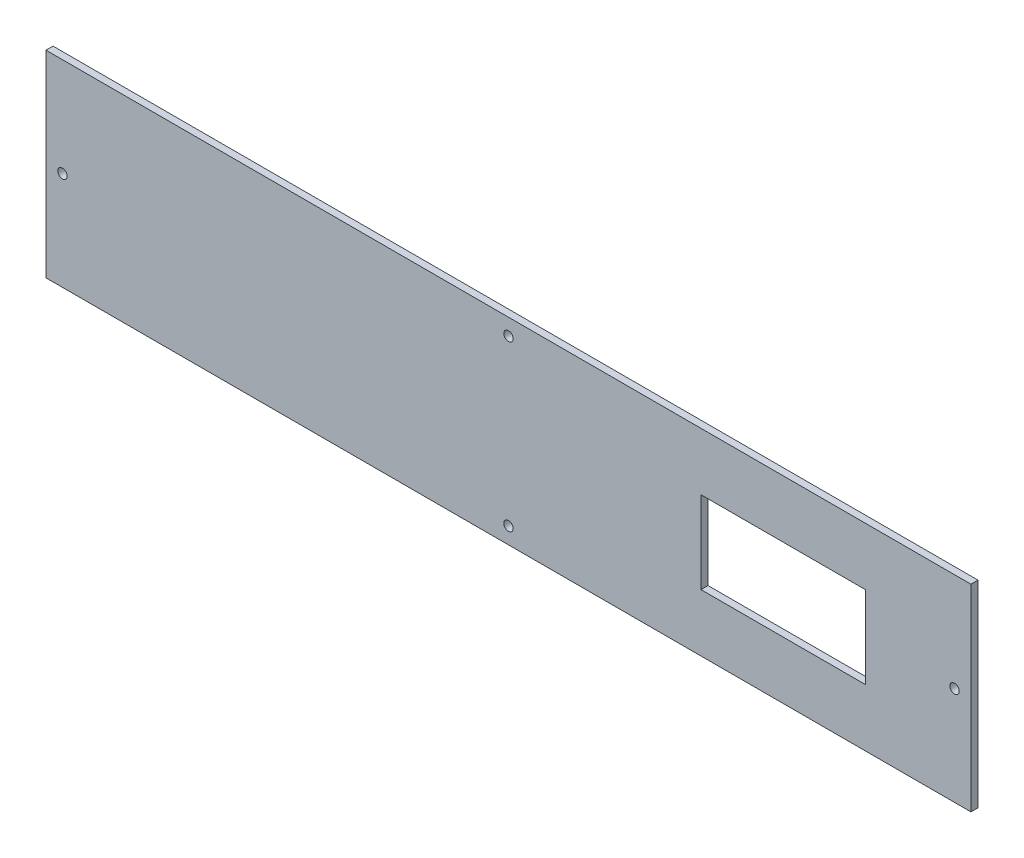
SolidWorks part; units mm, degrees
ref_plane "Piano frontale" through (0, 0, 0) normal (0, 0, 1) x (1, 0, 0)
ref_plane "Piano superiore" through (0, 0, 0) normal (0, 1, 0) x (1, 0, 0)
ref_plane "Piano destro" through (0, 0, 0) normal (1, 0, 0) x (0, 0, -1)
sketch "Schizzo1" plane through (0, 0, 0) normal (0, 0, 1) x (1, 0, 0)
  line L0 (0, 0) -> (0, 84)
  line L1 (0, 84) -> (394, 84)
  line L2 (394, 84) -> (394, 0)
  line L3 (394, 0) -> (0, 0)
  line L4 (0, 42) -> (394, 42) construction
  line L5 (197, 42) -> (197, 123.488) construction
  line L6 (279, 59.5) -> (279, 24.5)
  line L7 (279, 24.5) -> (349, 24.5)
  line L8 (349, 24.5) -> (349, 59.5)
  line L9 (349, 59.5) -> (279, 59.5)
  circle A0 centre (7, 42) radius 2
  circle A1 centre (197, 77) radius 2
  circle A2 centre (197, 7) radius 2
  circle A3 centre (387, 42) radius 2
  dimension "D3" = 7
  dimension "D4" = 7
  dimension "D6" = 4
  dimension "D1" = 84
  dimension "D2" = 394
  dimension "D5" = 45
  dimension "D7" = 70
  dimension "D8" = 35
extrude "Estrusione-Estrusione1" add sketch "Schizzo1" along normal blind 3
